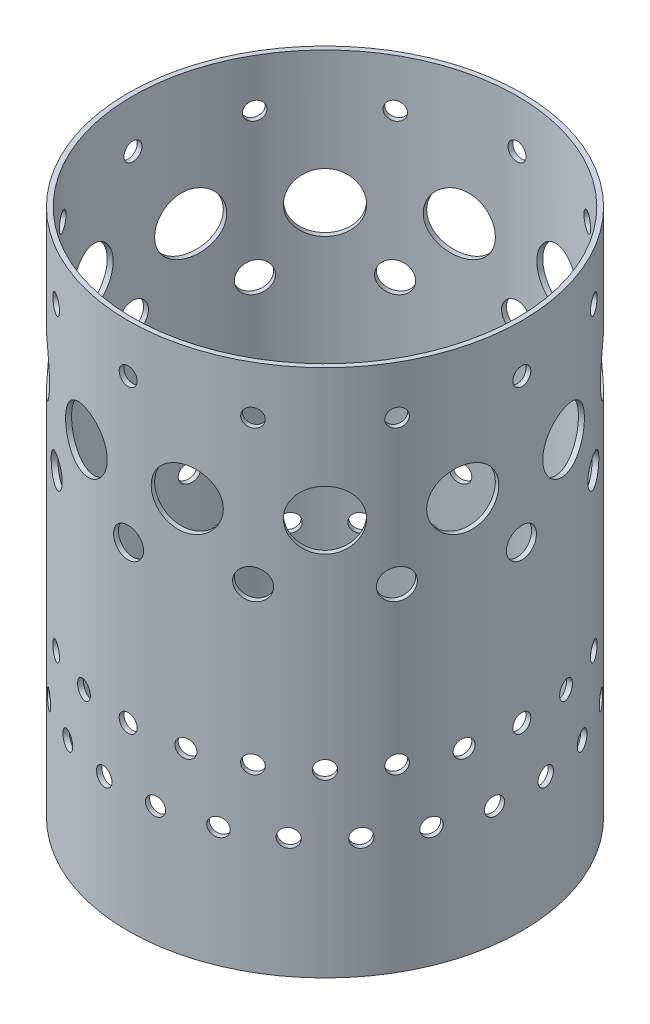
SolidWorks part; units mm, degrees
material "AISI Type 316L stainless steel"
ref_plane "Front Plane" through (0, 0, 0) normal (0, 0, 1) x (1, 0, 0)
ref_plane "Top Plane" through (0, 0, 0) normal (0, 1, 0) x (1, 0, 0)
ref_plane "Right Plane" through (0, 0, 0) normal (1, 0, 0) x (0, 0, -1)
sketch "Sketch1" plane through (0, 0, 0) normal (0, 1, 0) x (1, 0, 0)
  circle A0 centre (0, 0) radius 16.4
  dimension "D1" = 32.8
extrude "Extrude-Thin1" add sketch "Sketch1" along normal blind 44 thin thin type one direction reverse wall 0.4
sketch "Sketch3" plane through (0, 0, 0) normal (1, 0, 0) x (0, 0, -1)
  line L0 (0, 0) -> (0, 45.3222) construction
  line L2 (16.4, 44) -> (-16.4, 44) construction
  line L3 (16, 44) -> (-16, 44) construction
  circle A0 centre (0, 40) radius 0.75
  circle A1 centre (0, 28) radius 1.25
  circle A2 centre (0, 15) radius 0.75
  dimension "D1" = 1.5
  dimension "D2" = 2.5
  dimension "D3" = 1.5
  dimension "D4" = 4
  dimension "D5" = 16
  dimension "D6" = 13
extrude "Cut-Extrude1" cut sketch "Sketch3" along normal through all
ref_axis "Axis1" through (0, 44, 0) along (0, -1, 0)
ref_plane "Plane1" through (0, 0, 0) normal (0.9659, 0, 0.2588) x (0.2588, 0, -0.9659)
sketch "Sketch4" plane through (0, 0, 0) normal (0.9659, 0, 0.2588) x (0.2588, 0, -0.9659)
  line L0 (0, 44) -> (0, 0) construction
  line L1 (16.4, 44) -> (-16.4, 44) construction
  circle A0 centre (0, 15) radius 0.75
  circle A1 centre (0, 33) radius 2.45
  dimension "D1" = 4.9
  dimension "D2" = 1.5
  dimension "D3" = 11
  dimension "D4" = 29
extrude "Cut-Extrude2" cut sketch "Sketch4" along normal through all
ref_plane "Plane2" through (0, 0, 0) normal (0.9914, 0, 0.1305) x (0.1305, 0, -0.9914)
sketch "Sketch5" plane through (0, 0, 0) normal (0.9914, 0, 0.1305) x (0.1305, 0, -0.9914)
  line L0 (0, 44) -> (0, 0) construction
  line L1 (16.4, 44) -> (-16.4, 44) construction
  circle A0 centre (0, 10) radius 0.75
  dimension "D1" = 1.5
  dimension "D2" = 34
extrude "Cut-Extrude3" cut sketch "Sketch5" along normal through all
ref_plane "Plane3" through (0, 0, 0) normal (0.9914, 0, -0.1305) x (-0.1305, 0, -0.9914)
sketch "Sketch6" plane through (0, 0, 0) normal (0.9914, 0, -0.1305) x (-0.1305, 0, -0.9914)
  line L0 (0, 44) -> (0, 0) construction
  line L1 (16.4, 44) -> (-16.4, 44) construction
  circle A0 centre (0, 10) radius 0.75
  dimension "D1" = 1.5
  dimension "D2" = 34
extrude "Cut-Extrude4" cut sketch "Sketch6" along normal through all
pattern_circular "CirPattern2" count 12 over 360 about axis through (0, 44, 0) along (0, -1, 0) of "Cut-Extrude1", "Cut-Extrude2", "Cut-Extrude3", "Cut-Extrude4"
